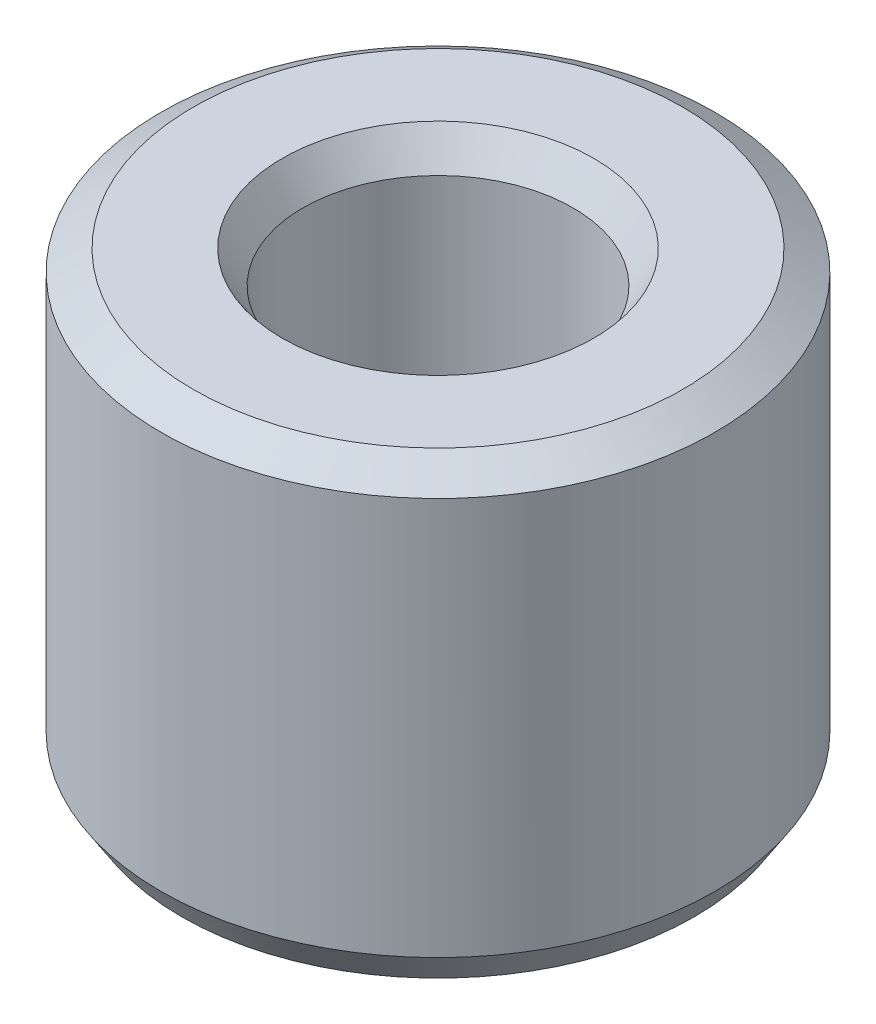
SolidWorks part; units mm, degrees
ref_plane "Front Plane" through (0, 0, 0) normal (0, 0, 1) x (1, 0, 0)
ref_plane "Top Plane" through (0, 0, 0) normal (0, 1, 0) x (1, 0, 0)
ref_plane "Right Plane" through (0, 0, 0) normal (1, 0, 0) x (0, 0, -1)
sketch "Sketch1" plane through (0, 0, 0) normal (0, 1, 0) x (1, 0, 0)
  circle A0 centre (0, 0) radius 35
  dimension "SLEEVE_OD" = 70
extrude "Boss-Extrude1" add sketch "Sketch1" along normal blind 56.9372
sketch "Sketch2" plane through (0, 0, 0) normal (0, 1, 0) x (1, 0, 0)
  circle A0 centre (0, 0) radius 17.0543
  dimension "BORE_D" = 34.1087
extrude "Cut-Extrude1" cut sketch "Sketch2" along normal through all
chamfer "Chamfer1" distance 2.6225 angle 57.387 4 edges at (0, 56.9372, 17.0543) (0, 0, 17.0543) (0, 0, 35) (0, 56.9372, 35) first distance on face at (0, 56.9372, 17.0543) first distance on face at (0, 0, 17.0543) first distance on face at (0, 56.9372, 35)
